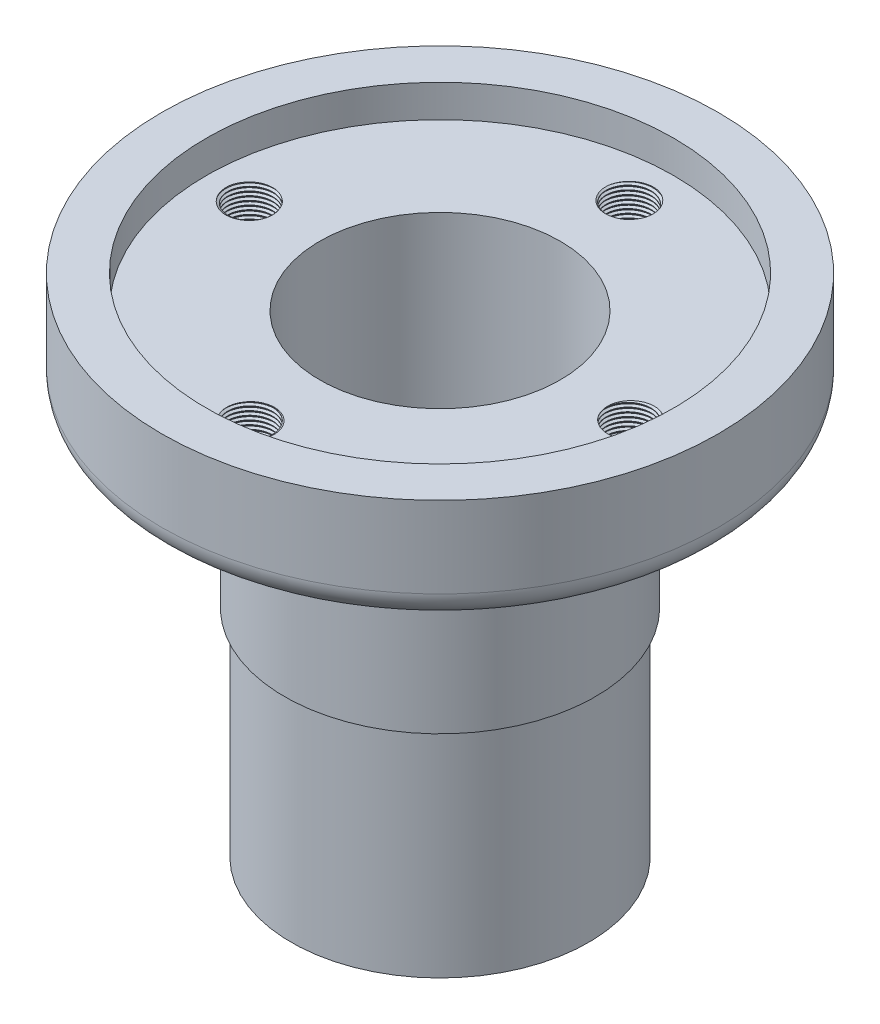
SolidWorks part; units mm, degrees
material "Stainless Steel (ferritic)"
ref_plane "Front Plane" through (0, 0, 0) normal (0, 0, 1) x (1, 0, 0)
ref_plane "Top Plane" through (0, 0, 0) normal (0, 1, 0) x (1, 0, 0)
ref_plane "Right Plane" through (0, 0, 0) normal (1, 0, 0) x (0, 0, -1)
sketch "Sketch1" plane through (0, 0, 0) normal (0, 0, 1) x (1, 0, 0)
  line L0 (1081, 0) -> (40.5, 0) construction
  line L1 (0, 0) -> (0, 85189.7881) construction
  line L2 (40.5, 0) -> (55, 0)
  line L3 (55, 0) -> (55, 80)
  line L4 (55, 80) -> (57.5, 80)
  line L5 (57.5, 80) -> (57.5, 127)
  line L6 (77.5, 147) -> (93, 147)
  line L7 (103, 157) -> (103, 187)
  line L8 (103, 187) -> (86.5081, 187)
  line L10 (40.5, 0) -> (40.5, 59)
  line L11 (40.5, 59) -> (36, 59)
  line L12 (36, 59) -> (36, 103)
  line L13 (36, 103) -> (44.5, 103)
  line L14 (0, 0) -> (-85189.7881, 0) construction
  line L15 (44.5, 175) -> (86.5081, 175)
  line L16 (86.5081, 175) -> (86.5081, 187)
  line L17 (44.5, 103) -> (44.5, 175)
  arc A0 (57.5, 127) -> (77.5, 147) centre (77.5, 127) cw
  arc A1 (93, 147) -> (103, 157) centre (93, 157) ccw
  point P15 (57.5, 147)
  point P19 (103, 147)
  dimension "D7" = 20
  dimension "D8" = 10
  dimension "D1" = 80
  dimension "D2" = 55
  dimension "D3" = 2.5
  dimension "D4" = 67
  dimension "D5" = 45.5
  dimension "D6" = 40
  dimension "D9" = 14.5
  dimension "D10" = 44
  dimension "D11" = 59
  dimension "D12" = 21.5
  dimension "D13" = 72
  dimension "D14" = 12
  dimension "D15" = 13
revolve "Revolve2" add sketch "Sketch1" angle 360 about L1
hole_wizard "Ø1.0mm Dowel Hole1" positions "Sketch2" profile "Sketch3" hole size "Ø1.0" standard "BSI"
sketch "Sketch2" plane through (0, 175, 0) normal (0, 1, 0) x (1, 0, 0)
  point P0 (0, 70)
  dimension "D1" = 70
sketch "Sketch3" plane through (0, 175, -70) normal (1, 0, 0) x (0, 0, 1)
  line L0 (0, 0) -> (0, 19.9571)
  line L1 (0, 19.9571) -> (8.25, 15)
  line L2 (8.25, 15) -> (8.25, 0)
  line L5 (8.25, 0) -> (0, 0)
  line L10 (0, 19.9571) -> (-8.25, 15) construction
  line L11 (0, -6.35) -> (0, 107.95) construction
  dimension "Hole Dia." = 16.5
  dimension "Hole Depth" = 15
  dimension "Drill Angle" = 118
pattern_circular "CirPattern1" count 4 over 360 about axis through (0, 187, 0) along (0, -1, 0) of "Ø1.0mm Dowel Hole1"
thread "Thread1" pitch 1.5 method cut profile "Thread Profile1" start angle 0, offset 5, length 20, pitch 1.5, diameter 16.5
ref_plane "Plane1" through (-78.25, 180, 0) normal (0, 0, -1) x (1, 0, 0)
sketch "Thread Profile1" plane through (-78.25, 180, 0) normal (0, 0, -1) x (1, 0, 0)
  line L0 (0, 0) -> (0, 1.5) construction
  line L11 (0, 0) -> (0, 1.3125)
  line L12 (0, 1.3125) -> (-0.8119, 0.8437)
  line L13 (-0.8119, 0.8437) -> (-0.8119, 0.4687)
  line L15 (-0.8119, 0.4687) -> (0, 0)
  line L17 (-0.8119, 0.6562) -> (0, 0.6562) construction
  point P2 (0, 0)
  dimension "Pitch" = 1.5
  dimension "Profile_Angle" = 60
  dimension "Profile_Land" = 0.375
  dimension "Profile_Height" = 0.8119
pattern_circular "CirPattern2" count 4 over 360 about axis through (0, 187, 0) along (0, -1, 0) of "Thread1"
